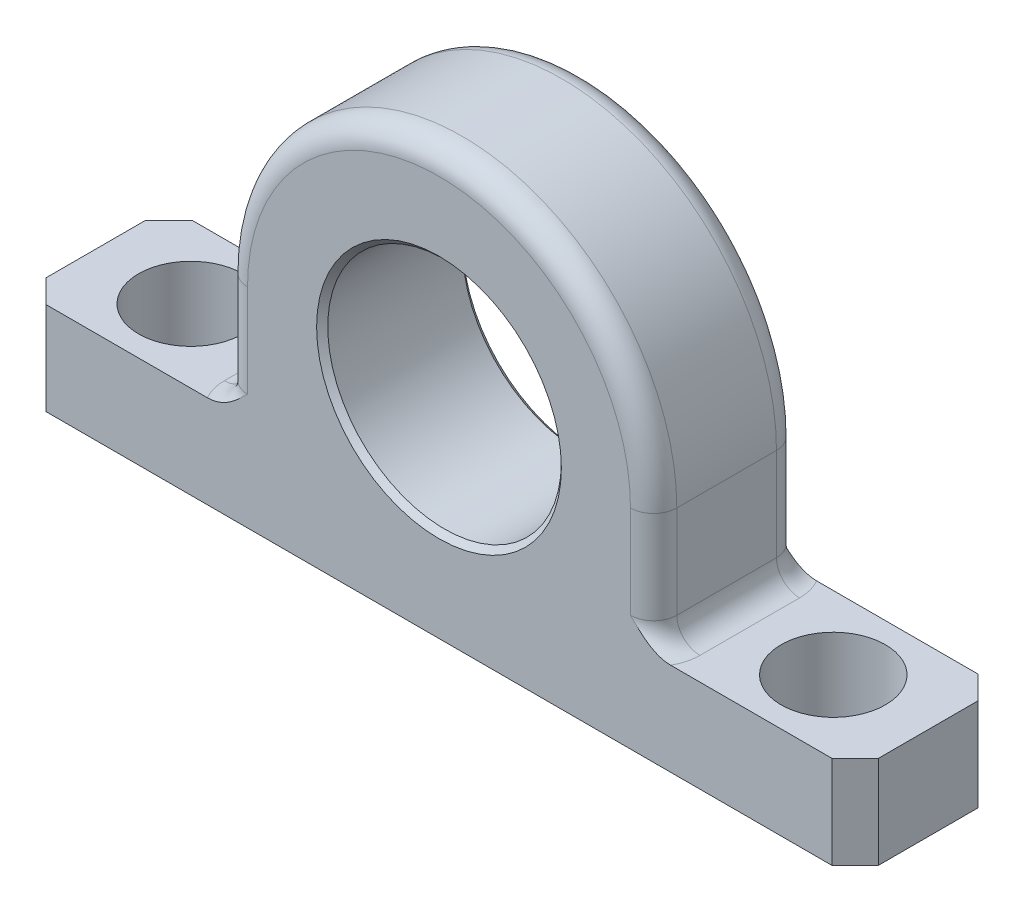
SolidWorks part; units mm, degrees
ref_plane "Front Plane" through (0, 0, 0) normal (0, 0, 1) x (1, 0, 0)
ref_plane "Top Plane" through (0, 0, 0) normal (0, 1, 0) x (1, 0, 0)
ref_plane "Right Plane" through (0, 0, 0) normal (1, 0, 0) x (0, 0, -1)
sketch "Sketch1" plane through (0, 0, 0) normal (0, 0, 1) x (1, 0, 0)
  line L0 (-28.5, 0) -> (28.5, 0) construction
  line L1 (28.5, 0) -> (28.5, 6.35) construction
  line L2 (28.5, 6.35) -> (14.7, 6.35) construction
  line L3 (14.7, 6.35) -> (14.7, 14.3) construction
  line L4 (0, 14.3) -> (0, 0) construction
  line L5 (-28.5, 0) -> (-28.5, 6.35) construction
  line L6 (-28.5, 6.35) -> (-14.7, 6.35) construction
  line L7 (-14.7, 6.35) -> (-14.7, 14.3) construction
  line L8 (-22, 6.35) -> (-22, 0) construction
  line L9 (22, 6.35) -> (22, 0) construction
  circle A0 centre (0, 14.3) radius 8 construction
  arc A1 (14.7, 14.3) -> (-14.7, 14.3) centre (0, 14.3) ccw construction
  point P4 (0, 0)
  point P18 (-25.5719, 6.35)
  point P19 (-18.4281, 6.35)
  point P21 (0, 29)
  dimension "ID" = 16
  dimension "Length (B)" = 57
  dimension "Height (D)" = 29
  dimension "Center Height (A)" = 14.3
  dimension "Center to Center (C)" = 44
  dimension "Mounting Hole Diameter (F)" = 7.1437
  dimension "Flange Thickness" = 6.35
sketch "Sketch2" plane through (0, 0, 0) normal (0, 0, 1) x (1, 0, 0)
  line L0 (-28.5, 0) -> (-28.5, 6.35) construction
  line L1 (-28.5, 0) -> (28.5, 0) construction
  line L2 (28.5, 0) -> (28.5, 6.35) construction
  line L3 (28.5, 6.35) -> (14.7, 6.35) construction
  line L4 (14.7, 6.35) -> (14.7, 14.3) construction
  line L5 (-14.7, 6.35) -> (-14.7, 14.3) construction
  line L6 (-28.5, 6.35) -> (-14.7, 6.35) construction
  line L7 (-28.5, 0) -> (-28.5, 6.35)
  line L8 (-28.5, 0) -> (28.5, 0)
  line L9 (28.5, 0) -> (28.5, 6.35)
  line L10 (28.5, 6.35) -> (14.7, 6.35)
  line L11 (14.7, 6.35) -> (14.7, 14.3)
  line L12 (-14.7, 6.35) -> (-14.7, 14.3)
  line L13 (-28.5, 6.35) -> (-14.7, 6.35)
  arc A0 (14.7, 14.3) -> (-14.7, 14.3) centre (0, 14.3) ccw construction
  arc A1 (14.7, 14.3) -> (-14.7, 14.3) centre (0, 14.3) ccw
  circle A2 centre (0, 14.3) radius 8 construction
  circle A3 centre (0, 14.3) radius 8
extrude "Body Extrude" add sketch "Sketch2" along normal mid plane 10
fillet "Body Fillet A" radius 1.5875 6 edges at (14.7, 10.325, 5) (0, 29, 5) (-14.7, 10.325, 5) (-14.7, 10.325, -5) (0, 29, -5) (14.7, 10.325, -5)
fillet "Body Fillet B" radius 1.5875 6 edges at (14.235, 6.35, 4.535) (14.235, 6.35, -4.535) (-14.235, 6.35, 4.535) (-14.235, 6.35, -4.535) (14.7, 6.35, 0) (-14.7, 6.35, 0)
chamfer "Chamfer2" distance 1.5875 angle 45 4 edges at (28.5, 3.175, -5) (28.5, 3.175, 5) (-28.5, 3.175, -5) (-28.5, 3.175, 5)
chamfer "ID Chamfer" distance 0.381 angle 45 2 edges at (8, 14.3, -5) (8, 14.3, 5)
sketch "Sketch3" plane through (0, 6.35, 0) normal (0, 1, 0) x (1, 0, 0)
  line L0 (-28.5, 0) -> (-14.7, 0) construction
  line L1 (0, 0) -> (0, 5) construction
  line L2 (8, 5) -> (-8, 5) construction
  circle A0 centre (-22, 0) radius 3.5719
  circle A1 centre (22, 0) radius 3.5719
extrude "Hole Cut" cut sketch "Sketch3" against normal through all
ref_axis "Center Axis 1" through (0, 14.3, 4.619) along (0, 0, -1)
ref_axis "Center Axis 2" through (-22, 0, 0) along (0, 1, 0)
ref_axis "Center Axis 3" through (22, 0, 0) along (0, 1, 0)
ref_plane "Contact Plane 1" through (0, 0, 0) normal (0, -1, 0) x (-1, 0, 0)
equation "\"D1@Body Fillet B\" = \"Radius@Body Fillet A\""
equation "\"D1@Chamfer2\"=\"Radius@Body Fillet A\""
